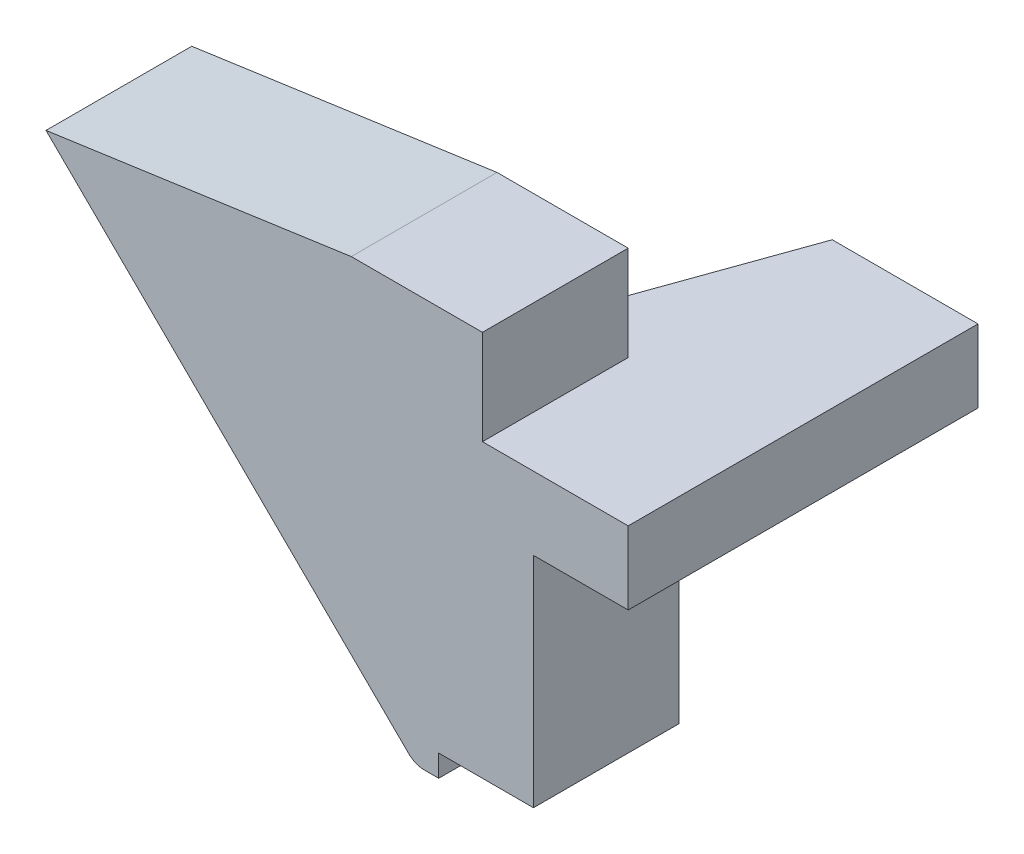
SolidWorks part; units mm, degrees
ref_plane "Front" through (0, 0, 0) normal (0, 0, 1) x (1, 0, 0)
ref_plane "Top" through (0, 0, 0) normal (0, 1, 0) x (1, 0, 0)
ref_plane "Right" through (0, 0, 0) normal (1, 0, 0) x (0, 0, -1)
sketch "草图1" plane through (0, 0, 0) normal (0, 0, 1) x (1, 0, 0)
  line L0 (0, 0) -> (0, 40)
  line L1 (0, 40) -> (-5, 40)
  line L2 (0, 0) -> (-5, 0)
  line L3 (-5, 0) -> (-5, -3)
  line L4 (-5, -3) -> (-13, -3)
  line L5 (-5, 53) -> (-23, 53)
  line L6 (-5, 40) -> (-5, 53)
  line L8 (-15.1213, -2.1213) -> (-64.8886, 47.0507)
  line L10 (-23, 53) -> (-64.8886, 47.0507)
  arc A0 (-15.1213, -2.1213) -> (-13, -3) centre (-13, 0) ccw
extrude "凸台-拉伸1" add sketch "草图1" along normal blind 172
shell "抽壳1" thickness 6
sketch "草图2" plane through (0, 0, 0) normal (1, 0, 0) x (0, 0, -1)
  line L1 (-154, 2) -> (-154, 18)
  line L2 (-154, 18) -> (-118, 18)
  line L3 (-118, 18) -> (-118, 2)
  line L4 (-54, 2) -> (-54, 18)
  line L5 (-54, 18) -> (-18, 18)
  line L6 (-18, 2) -> (-18, 18)
  line L7 (-54, 2) -> (-18, 2)
  line L9 (-154, 2) -> (-118, 2)
extrude "切除-拉伸1" cut sketch "草图2" against normal blind 74
ref_plane "基准面1" through (0, 0, 86) normal (0, 0, -1) x (-1, 0, 0)
sketch "草图3" plane through (0, 0, 86) normal (0, 0, -1) x (-1, 0, 0)
  line L0 (5, 53) -> (5, 40)
  line L1 (5, 40) -> (0, 40)
  line L2 (0, 40) -> (0, 0)
  line L3 (0, 0) -> (5, 0)
  line L4 (5, 0) -> (5, -3)
  line L5 (5, -3) -> (13, -3)
  line L6 (13, -3) -> (16.5794, -0.6807)
  line L7 (64.8886, 47.0507) -> (15.1213, -2.1213) construction
  line L8 (16.5794, -0.6807) -> (64.8886, 47.0507)
  line L9 (64.8886, 47.0507) -> (23, 53)
  line L10 (23, 53) -> (5, 53)
extrude "凸台-拉伸2" add sketch "草图3" along normal mid plane 4 contours L8 L9 L10 L0 L1 L2 L3 L4 L5 L6
sketch "草图4" plane through (0, 0, 172) normal (0, 0, 1) x (1, 0, 0)
  circle A0 centre (-15, 21.0713) radius 10
extrude "切除-拉伸2" cut sketch "草图4" against normal blind 186
sketch "草图5" plane through (0, 53, 0) normal (0, 1, 0) x (1, 0, 0)
  circle A1 centre (-13.3382, -63.5) radius 1.5
  circle A2 centre (-13.3382, -108.5) radius 1.5
extrude "切除-拉伸3" cut sketch "草图5" against normal blind 10
sketch "草图6" plane through (0, 0, 172) normal (0, 0, 1) x (1, 0, 0)
  line L0 (-11, 6) -> (-14.8042, 6)
  line L1 (-52.062, 42.8122) -> (-11.7678, 3) construction
  line L2 (-14.8042, 6) -> (-11.7678, 3)
  line L3 (-11.7678, 3) -> (-11, 3)
  line L4 (-11, 3) -> (-11, 6)
extrude "凸台-拉伸3" add sketch "草图6" against normal blind 172
sketch "草图7" plane through (0, 0, 0) normal (1, 0, 0) x (0, 0, -1)
  line L0 (-154, 18) -> (-154, 2)
  line L1 (-154, 2) -> (-118, 2)
  line L2 (-118, 2) -> (-118, 18)
  line L3 (-118, 18) -> (-154, 18)
  line L4 (-54, 18) -> (-54, 2)
  line L5 (-54, 2) -> (-18, 2)
  line L6 (-18, 2) -> (-18, 18)
  line L7 (-18, 2) -> (-18, 18) construction
  line L8 (-18, 18) -> (-54, 18) construction
  line L9 (-18, 18) -> (-54, 18)
extrude "切除-拉伸4" cut sketch "草图7" against normal blind 172
sketch "草图8" plane through (0, -3, 0) normal (0, -1, 0) x (1, 0, 0)
  line L0 (-5, 172) -> (-11, 172)
  line L1 (-13, 172) -> (-5, 172) construction
  line L2 (-11, 172) -> (-11, 0)
  line L3 (-13, 0) -> (-5, 0) construction
  line L4 (-11, 0) -> (-5, 0)
  line L5 (-5, 0) -> (-5, 172)
extrude "切除-拉伸5" cut sketch "草图8" against normal blind 3
sketch "草图9" plane through (0, 0, 0) normal (1, 0, 0) x (0, 0, -1)
  line L0 (-86, 40) -> (-151, 40)
  line L1 (-172, 40) -> (0, 40) construction
  line L2 (-151, 40) -> (-151, 35)
  line L3 (-151, 35) -> (-86, 35)
  line L4 (-86, -55) -> (-86, 55) construction
  line L5 (-86, 35) -> (-21, 35)
  line L6 (-21, 35) -> (-21, 40)
  line L7 (-21, 40) -> (-86, 40)
extrude "凸台-拉伸4" add sketch "草图9" along normal blind 15
chamfer "倒角1" distance 15 angle 45 1 edges at (15, 37.5, 151)
chamfer "倒角2" distance 15 angle 45 1 edges at (15, 37.5, 21)
chamfer "倒角3" distance 8 angle 45 1 edges at (0, 35, 86)
sketch "草图10" plane through (0, 0, 0) normal (0, -1, 0) x (1, 0, 0)
  circle A2 centre (-5, 158) radius 1.35
  circle A3 centre (-5, 111) radius 1.35
  circle A4 centre (-5, 61) radius 1.35
  circle A5 centre (-5, 14.0136) radius 1.35
extrude "切除-拉伸6" cut sketch "草图10" against normal blind 15
sketch "草图12" plane through (0, 40, 0) normal (0, 1, 0) x (1, 0, 0)
  line L2 (55, -86) -> (-55, -86) construction
  circle A1 centre (5, -41) radius 1.35
  circle A2 centre (5, -86) radius 1.35
  circle A3 centre (5, -131) radius 1.35
extrude "切除-拉伸7" cut sketch "草图12" against normal blind 15
sketch "草图14" plane through (0, 0, 0) normal (1, 0, 0) x (0, 0, -1)
  line L0 (-83.1596, 53) -> (-83.1596, -3)
  line L1 (-172, 53) -> (0, 53) construction
  line L2 (-172, -3) -> (0, -3) construction
  line L3 (-83.1596, -3) -> (-68.1596, -3)
  line L4 (-68.1596, -3) -> (-68.1596, 53)
  line L5 (-68.1596, 53) -> (-83.1596, 53)
  point P8 (-83.1596, 53)
extrude "切除-拉伸8" cut sketch "草图14" against normal mid plane 165 flip side to cut
sketch "草图15" plane through (0, 0, 68.1596) normal (0, 0, -1) x (-1, 0, 0)
  line L0 (0, 0) -> (-2, 0)
  line L1 (-2, 0) -> (-2, 29)
  line L2 (-8, 35) -> (0, 27) construction
  line L3 (-2, 29) -> (0, 27)
  line L4 (0, 27) -> (0, 0)
extrude "凸台-拉伸5" add sketch "草图15" against normal blind 15
sketch "草图16" plane through (0, 0, 68.1596) normal (0, 0, -1) x (-1, 0, 0)
  line L0 (-2, 29) -> (-2, 35)
  line L1 (-8, 35) -> (-2, 35)
  line L2 (-8, 35) -> (-2, 29)
extrude "切除-拉伸9" cut sketch "草图16" against normal blind 15
sketch "草图17" plane through (0, 0, 68.1596) normal (0, 0, -1) x (-1, 0, 0)
  line L0 (-15, 35) -> (-15, 30)
  line L1 (-15, 30) -> (-2, 30)
  line L2 (-2, 35) -> (-2, 0) construction
  line L3 (-2, 30) -> (-2, 35)
  line L4 (-2, 35) -> (-15, 35)
extrude "凸台-拉伸6" add sketch "草图17" against normal blind 15
sketch "草图18" plane through (0, 0, 68.1596) normal (0, 0, -1) x (-1, 0, 0)
  line L0 (-15, 40) -> (-15, 30)
  line L1 (-15, 30) -> (-2, 30)
  line L2 (-2, 30) -> (-2, 0)
  line L3 (-2, 0) -> (11, 0)
  line L4 (11, 0) -> (11, -3)
  line L5 (11, -3) -> (13, -3)
  line L6 (15.1213, -2.1213) -> (64.8886, 47.0507)
  line L7 (64.8886, 47.0507) -> (23, 53)
  line L8 (23, 53) -> (5, 53)
  line L9 (5, 53) -> (5, 40)
  line L10 (5, 40) -> (-15, 40)
  arc A0 (13, -3) -> (15.1213, -2.1213) centre (13, 0) ccw
extrude "凸台-拉伸7" add sketch "草图18" against normal blind 20 contours L10 L0 L1 L2 L3 L4 L5 A0 L6 L7 L8 L9
shell "抽壳2" thickness 10 removed face at (-9.5081, 23.7265, 88.1596)
sketch "草图20" plane through (0, 0, 88.1596) normal (0, 0, 1) x (1, 0, 0)
  line L0 (15, 40) -> (-15, 40)
  line L1 (-15, 43) -> (-15, 30) construction
  line L2 (-15, 40) -> (-15, 30)
  line L3 (-15, 30) -> (-8, 30)
  line L4 (-8, 30) -> (-8, 10) construction
  line L5 (-8, 30) -> (-8, 10) construction
  line L6 (-8, 30) -> (-8, 22)
  line L7 (-8, 22) -> (2, 22)
  line L8 (2, 30) -> (2, 0) construction
  line L9 (2, 22) -> (2, 30)
  line L10 (2, 30) -> (15, 30)
  line L11 (15, 30) -> (15, 40)
extrude "凸台-拉伸8" add sketch "草图20" along normal blind 28
sketch "草图21" plane through (2, 0, 0) normal (1, 0, 0) x (0, 0, -1)
  line L0 (-116.1596, 30) -> (-88.1596, 22)
  line L1 (-88.1596, 22) -> (-116.1596, 22)
  line L2 (-116.1596, 22) -> (-116.1596, 30)
extrude "切除-拉伸10" cut sketch "草图21" against normal blind 20
sketch "草图22" plane through (0, 40, 0) normal (0, 1, 0) x (1, 0, 0)
  line L1 (-8, -116.1596) -> (-15, -116.1596)
  line L2 (-15, -116.1596) -> (-15, -88.1596)
  line L4 (15, -116.1596) -> (-15, -116.1596) construction
  line L5 (-5, -116.1596) -> (-8, -116.1596)
  line L6 (-5, -116.1596) -> (-15, -88.1596)
extrude "切除-拉伸11" cut sketch "草图22" against normal blind 20
ref_plane "基准面2" through (0, 0, 126.1596) normal (0, 0, 1) x (1, 0, 0)
mirror "镜向6" about plane through (0, 0, 126.1596) normal (0, 0, 1) of bodies 119
sketch "草图24" plane through (0, 40, 0) normal (0, 1, 0) x (1, 0, 0)
  line L0 (-102.3942, -125.7266) -> (32.7763, -125.7266)
  line L1 (32.7763, -125.7266) -> (42.6481, -30.5615)
  line L2 (42.6481, -30.5615) -> (-60.0725, -35.6441)
  line L3 (-60.0725, -35.6441) -> (-102.3942, -125.7266)
extrude "切除-拉伸12" cut sketch "草图24" against normal mid plane 126
